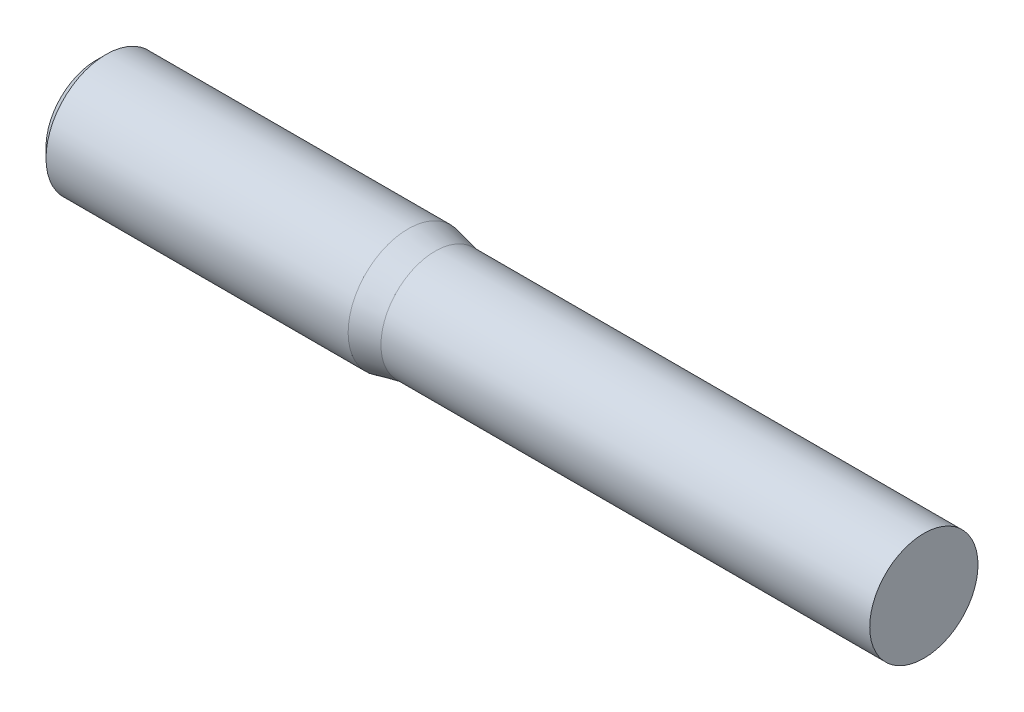
SolidWorks part; units mm, degrees
ref_plane "Front" through (0, 0, 0) normal (0, 0, 1) x (1, 0, 0)
ref_plane "Top" through (0, 0, 0) normal (0, 1, 0) x (1, 0, 0)
ref_plane "Right" through (0, 0, 0) normal (1, 0, 0) x (0, 0, -1)
sketch "Sketch1" plane through (0, 0, 0) normal (0, 0, 1) x (1, 0, 0)
  line L0 (0, 0) -> (25.0352, 0) construction
  line L1 (0, 0) -> (0, 5)
  line L2 (0, 5) -> (26, 5)
  line L3 (26, 5) -> (28.25, 4.513)
  line L4 (28.25, 4.513) -> (65, 4.513)
  line L5 (65, 4.513) -> (65, 0)
  line L7 (0, 0) -> (65, 0)
  dimension "D2" = 9.026
  dimension "l1" = 65
revolve "Base" add sketch "Sketch1" angle 360 about L0
cosmetic thread "ThreadCosmetic1" [suppressed] parameters "D1"=20, "D2"=8.376
chamfer "HeadChamfer" distance 0.812 angle 45 1 edges at (0, 0, 5)
sketch "Sketch2" plane through (65, 0, 0) normal (1, 0, 0) x (0, 0, -1)
  circle A0 centre (0, 0) radius 4.513 construction
  circle A1 centre (0, 0) radius 4.513
extrude "BaseEnd" add sketch "Sketch2" along normal blind 4
sketch "Sketch3" plane through (0, 0, 0) normal (0, 0, 1) x (1, 0, 0)
  line L0 (0.812, 4.2968) -> (1.218, 5)
  line L1 (1.218, 5) -> (1.218, 5.5)
  line L2 (1.218, 5.5) -> (0.406, 5.5)
  line L3 (0.406, 5.5) -> (0.406, 5)
  line L4 (0.406, 5) -> (0.812, 4.2968)
  line L5 (0, 0) -> (6.1546, 0) construction
  line L6 (0.812, 5) -> (0.812, -5) construction
  dimension "D1" = 60
  dimension "D2" = 0.812
  dimension "D3" = 0.5
  dimension "D4" = 10
  dimension "D5" = 60
revolve "Cut-Revolve10" [suppressed] cut sketch "Sketch3" angle 360 about L5
pattern_linear "LPattern10" [suppressed] count 27 spacing 0.9744 along (1, 0, 0) of bodies 103
equation "\"D1@HeadChamfer\" =  ( \"d@Sketch1\" - \"D2@ThreadCosmetic1\" )  / 2"
equation "\"D4@Sketch3\" = \"d@Sketch1\""
equation "\"D2@Sketch3\" =  ( \"d@Sketch1\" - \"D2@ThreadCosmetic1\" )  / 2"
equation "\"D3@LPattern10\" = \"D2@Sketch3\" * 1.2"
equation "\"D1@LPattern10\" = \"b@Sketch1\" / \"D3@LPattern10\""
